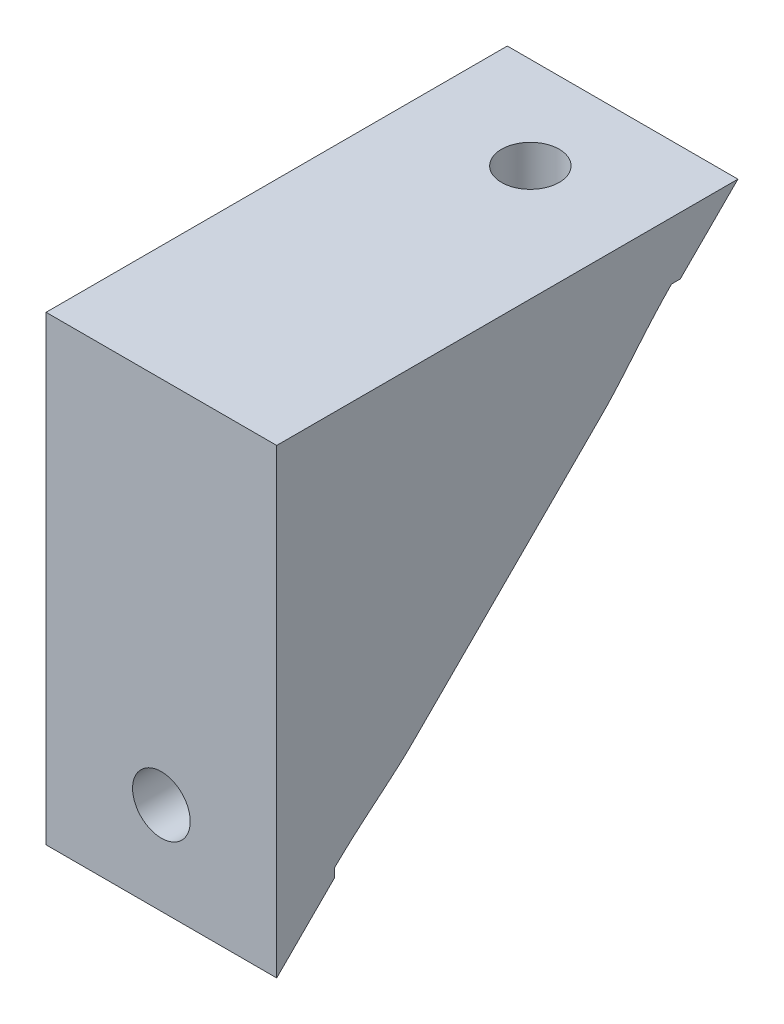
SolidWorks part; units mm, degrees
ref_plane "Front Plane" through (0, 0, 0) normal (0, 0, 1) x (1, 0, 0)
ref_plane "Top Plane" through (0, 0, 0) normal (0, 1, 0) x (1, 0, 0)
ref_plane "Right Plane" through (0, 0, 0) normal (1, 0, 0) x (0, 0, -1)
sketch "Sketch1" plane through (0, 0, 0) normal (1, 0, 0) x (0, 0, -1)
  line L0 (0, 0) -> (25.4, 0)
  line L1 (25.4, 0) -> (0, -25.4)
  line L2 (0, -25.4) -> (0, 0)
  dimension "D1" = 25.4
  dimension "D2" = 25.4
  dimension "D3" = 45
extrude "Boss-Extrude1" add sketch "Sketch1" along normal blind 12.7 contours L2 L1 L0 region at (0, -8.4667, -8.4667)
ref_plane "Plane1" through (0, -3.175, 0) normal (0, 1, 0) x (1, 0, 0)
sketch "Sketch2" plane through (0, -3.175, 0) normal (0, 1, 0) x (1, 0, 0)
  line L0 (0, 0) -> (0, 25.4) construction
  line L1 (12.7, 25.4) -> (0, 25.4) construction
  circle A0 centre (6.35, 20.32) radius 1.5875
  dimension "D1" = 3.175
  dimension "D2" = 6.35
  dimension "D3" = 5.08
extrude "Cut-Extrude1" cut sketch "Sketch2" against normal blind 19.05 and the other way blind 19.05
sketch "Sketch3" plane through (0, -3.175, 0) normal (0, 1, 0) x (1, 0, 0)
  circle A0 centre (6.35, 20.32) radius 5.08
  dimension "D1" = 10.16
extrude "Cut-Extrude2" cut sketch "Sketch3" against normal blind 19.05
ref_plane "Plane2" through (0, 0, -3.175) normal (0, 0, 1) x (1, 0, 0)
sketch "Sketch4" plane through (0, 0, -3.175) normal (0, 0, 1) x (1, 0, 0)
  line L0 (12.7, -25.4) -> (12.7, 0) construction
  line L2 (12.7, -25.4) -> (0, -25.4) construction
  circle A0 centre (6.35, -20.32) radius 1.5875
  dimension "D1" = 3.175
  dimension "D2" = 6.35
  dimension "D3" = 5.08
extrude "Cut-Extrude3" cut sketch "Sketch4" against normal blind 19.05 and the other way blind 19.05
sketch "Sketch5" plane through (0, 0, -3.175) normal (0, 0, 1) x (1, 0, 0)
  circle A0 centre (6.35, -20.32) radius 5.08
  dimension "D1" = 10.16
extrude "Cut-Extrude4" cut sketch "Sketch5" against normal blind 19.05
fillet "Fillet1" radius 2.54 2 edges at (6.35, -15.24, -10.16) (6.35, -10.16, -15.24)
